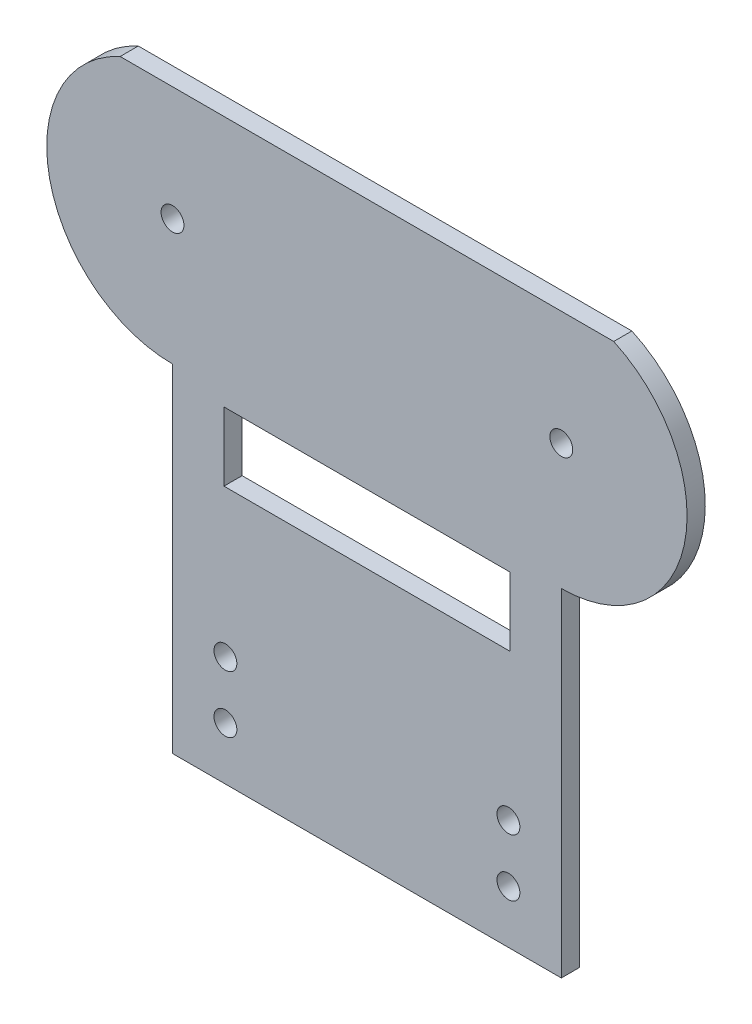
SolidWorks part; units mm, degrees
ref_plane "Front Plane" through (0, 0, 0) normal (0, 0, 1) x (1, 0, 0)
ref_plane "Top Plane" through (0, 0, 0) normal (0, 1, 0) x (1, 0, 0)
ref_plane "Right Plane" through (0, 0, 0) normal (1, 0, 0) x (0, 0, -1)
sketch "Sketch1" plane through (0, 0, 0) normal (0, 0, 1) x (1, 0, 0)
  line L0 (90, 70) -> (90, 0) construction
  line L2 (0, 0) -> (0, 70) construction
  line L3 (46.8348, 70) -> (133.1652, 70)
  line L4 (180, 0) -> (180, 70) construction
  line L5 (56, 28) -> (56, 0)
  line L6 (124, 28) -> (124, 0)
  line L7 (0, 70) -> (46.8348, 70) construction
  line L8 (133.1652, 70) -> (180, 70) construction
  line L9 (0, 0) -> (56, 0) construction
  line L10 (124, 0) -> (180, 0) construction
  line L11 (56, 0) -> (124, 0) construction
  line L12 (56, 0) -> (56, -31)
  line L13 (56, -31) -> (124, -31)
  line L14 (124, -31) -> (124, 0)
  circle A0 centre (56, 50) radius 2
  circle A1 centre (124, 50) radius 2
  arc A2 (46.8348, 70) -> (56, 28) centre (56, 50) ccw
  arc A3 (133.1652, 70) -> (124, 28) centre (124, 50) cw
  dimension "D3" = 4
  dimension "D7" = 46.8348
  dimension "D8" = 22
  dimension "D1" = 70
  dimension "D2" = 180
  dimension "D4" = 68
  dimension "D5" = 34
  dimension "D6" = 31
  dimension "D9" = 56
extrude "Boss-Extrude1" add sketch "Sketch1" along normal blind 3.175
sketch "Sketch2" plane through (0, 0, 3.175) normal (0, 0, 1) x (1, 0, 0)
  line L0 (133.1652, 70) -> (46.8348, 70) construction
  line L1 (65, 14) -> (115, 14)
  line L2 (65, 14) -> (65, 26)
  line L3 (65, 26) -> (115, 26)
  line L4 (115, 14) -> (115, 26)
  line L5 (65, 14) -> (115, 26) construction
  line L6 (65, 26) -> (115, 14) construction
  line L7 (56, 28) -> (56, -31) construction
  line L8 (56, -31) -> (124, -31) construction
  circle A0 centre (65.25, -21.75) radius 2
  circle A1 centre (65.25, -11.75) radius 2
  circle A2 centre (114.75, -11.75) radius 2
  circle A3 centre (114.75, -21.75) radius 2
  point P0 (90, 20)
  point P11 (0, 0)
  dimension "D5" = 4
  dimension "D1" = 50
  dimension "D2" = 34
  dimension "D3" = 50
  dimension "D4" = 12
  dimension "D6" = 9.25
  dimension "D7" = 9.25
  dimension "D10" = 10
  dimension "D11" = 49.5
  dimension "D12" = 9.25
  dimension "D8" = 2
  dimension "D9" = 2
extrude "Cut-Extrude1" cut sketch "Sketch2" against normal up to surface (3.175 mm away) up to face at (90, 21.1032, 0)
